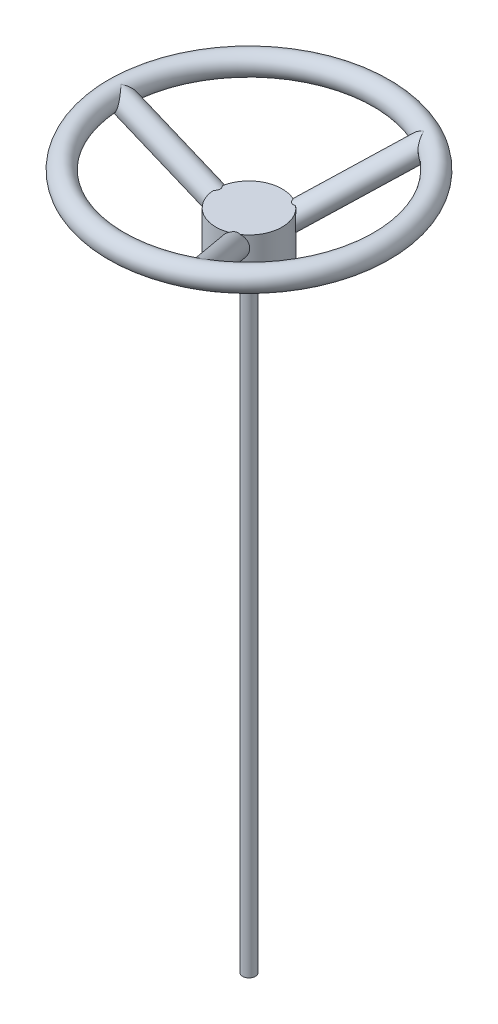
SolidWorks part; units mm, degrees
ref_plane "Front Plane" through (0, 0, 0) normal (0, 0, 1) x (1, 0, 0)
ref_plane "Top Plane" through (0, 0, 0) normal (0, 1, 0) x (1, 0, 0)
ref_plane "Right Plane" through (0, 0, 0) normal (1, 0, 0) x (0, 0, -1)
sketch "Sketch1" plane through (0, 0, 0) normal (0, 0, 1) x (1, 0, 0)
  line L0 (0, 0) -> (152.4, 0) construction
  line L1 (152.4, -24.1715) -> (152.4, 24.1715) construction
  circle A0 centre (0, 0) radius 12.7
  point P7 (152.4, 0)
  dimension "D1" = 25.4
  dimension "D2" = 152.4
revolve "Revolve1" add sketch "Sketch1" angle 360 about L1
sketch "Sketch3" plane through (0, 0, 0) normal (0, 1, 0) x (1, 0, 0)
  circle A0 centre (152.4, 0) radius 38.1 construction
  dimension "D1" = 76.2
  dimension "D2" = 152.4
ref_plane "Plane1" through (0, -38.1, 0) normal (0, 1, 0) x (1, 0, 0)
sketch "Sketch4" plane through (0, -38.1, 0) normal (0, 1, 0) x (1, 0, 0)
  circle A0 centre (152.4, 0) radius 38.1
extrude "Boss-Extrude1" add sketch "Sketch4" against normal blind 50.8 separate body
sketch3d "3DSketch1"
  line L0 (114.369, -50.8, -2.2918) -> (0, 0, 0)
  line L1 (114.369, -38.1, -2.2918) -> (114.369, -50.8, -2.2918) construction
  circle A0 centre (152.4, -38.1, 0) radius 38.1 construction
  point P5 (152.4, 0, 0)
  dimension "D1" = 12.7
sweep "Sweep1" add path "3DSketch1" circular profile diameter 25.4 parameters "D3"=25.4
sketch "Sketch13" plane through (114.369, -50.8, -2.2918) normal (0.9137, -0.4059, -0.0183) x (-0.0167, 0.0074, -0.9998)
  circle A0 centre (0, 0) radius 12.7
extrude "Boss-Extrude2" add sketch "Sketch13" along normal blind 50.8
pattern_circular "CirPattern1" count 3 over 360 about axis through (152.4, -38.1, 0) along (0, 1, 0) of "Sweep1", "Boss-Extrude2"
sketch "Sketch20" plane through (0, -88.9, 0) normal (0, -1, 0) x (-1, 0, 0)
  circle A0 centre (-152.4, 0) radius 7.3025
  dimension "D1" = 14.605
extrude "Boss-Extrude3" add sketch "Sketch20" along normal blind 711.2
